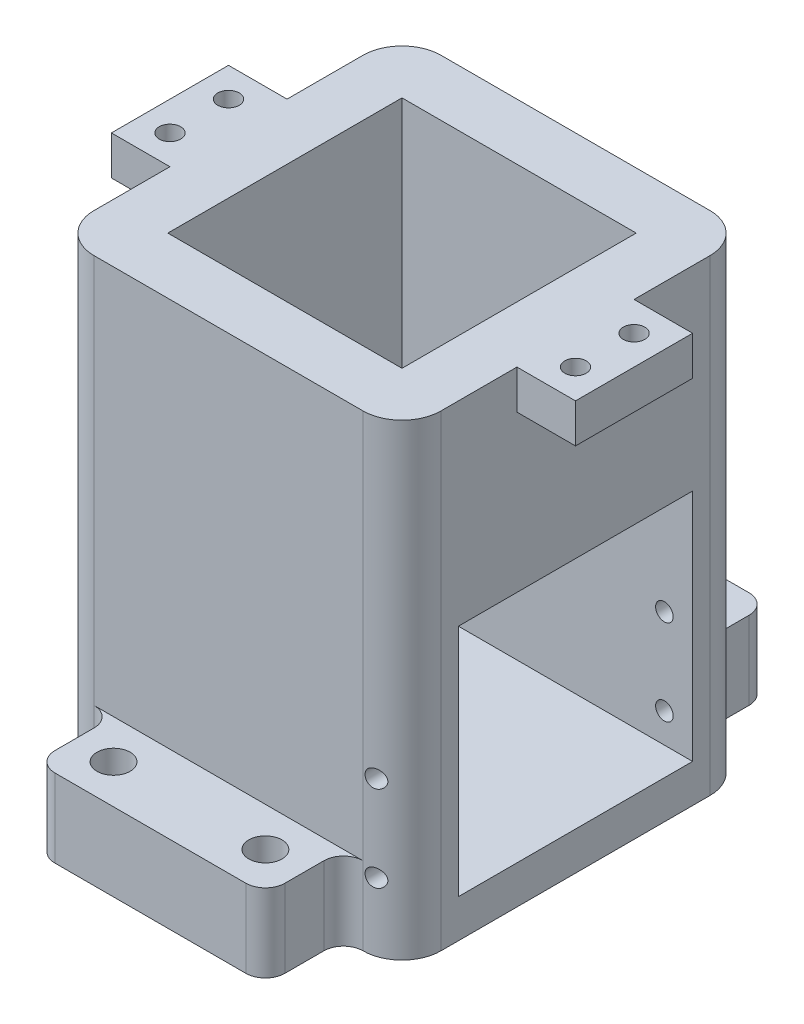
SolidWorks part; units mm, degrees
ref_plane "Front Plane" through (0, 0, 0) normal (0, 0, 1) x (1, 0, 0)
ref_plane "Top Plane" through (0, 0, 0) normal (0, 1, 0) x (1, 0, 0)
ref_plane "Right Plane" through (0, 0, 0) normal (1, 0, 0) x (0, 0, -1)
sketch "Sketch3" plane through (0, 0, 0) normal (0, 1, 0) x (1, 0, 0)
  line L1 (0, 0) -> (88.9, 0)
  line L2 (0, 0) -> (0, 88.9)
  line L3 (0, 88.9) -> (88.9, 88.9)
  line L4 (88.9, 0) -> (88.9, 88.9)
  dimension "D1" = 88.9
  dimension "D2" = 88.9
extrude "Boss-Extrude2" add sketch "Sketch3" along normal blind 50.8
ref_plane "Plane1" through (44.45, 0, 0) normal (-1, 0, 0) x (0, 0, 1)
sketch "Sketch5" plane through (0, 50.8, 0) normal (0, 1, 0) x (1, 0, 0)
  line L6 (0, 0) -> (88.9, 0)
  line L7 (0, 0) -> (0, 88.9)
  line L8 (0, 88.9) -> (88.9, 88.9)
  line L9 (88.9, 0) -> (88.9, 88.9)
sketch "Sketch7" plane through (0, 0, 0) normal (0, -1, 0) x (1, 0, 0)
  line L0 (44.45, -44.45) -> (65.45, -44.45)
  line L1 (44.45, 27.94) -> (44.45, -27.94) construction
  line L2 (65.45, -44.45) -> (65.45, -24.45)
  line L3 (65.45, -24.45) -> (23.45, -24.45)
  line L4 (23.45, -24.45) -> (23.45, -66.45)
  line L5 (23.45, -66.45) -> (65.45, -66.45)
  line L6 (65.45, -66.45) -> (65.45, -44.45)
  line L7 (44.45, -44.45) -> (44.45, -23.45)
  line L8 (44.45, -44.45) -> (44.45, -65.45)
  dimension "D1" = 21
  dimension "D3" = 42
  dimension "D4" = 42
  dimension "D5" = 21
  dimension "D6" = 21
sketch "Sketch10" plane through (0, 0, 0) normal (-1, 0, 0) x (0, 0, 1)
  line L1 (-73.9, 41) -> (-53.9, 41)
  line L2 (-73.9, 41) -> (-73.9, 61)
  line L3 (-73.9, 61) -> (-53.9, 61)
  line L4 (-53.9, 41) -> (-53.9, 61)
  line L5 (-88.9, 50.8) -> (-88.9, 0) construction
  line L6 (-35, 43.1973) -> (-15, 43.1973)
  line L7 (-35, 43.1973) -> (-35, 63.1973)
  line L8 (-35, 63.1973) -> (-15, 63.1973)
  line L9 (-15, 43.1973) -> (-15, 63.1973)
  line L11 (-88.9, 0) -> (0, 0) construction
  dimension "D1" = 20
  dimension "D2" = 20
  dimension "D3" = 20
  dimension "D4" = 20
  dimension "D5" = 18.9
  dimension "D6" = 15
  dimension "D7" = 41
sketch "Sketch11" plane through (88.9, 0, 0) normal (1, 0, 0) x (0, 0, -1)
  line L0 (0, 0) -> (88.9, 0) construction
  line L1 (15, 0) -> (35, 0)
  line L2 (15, 0) -> (15, 20)
  line L3 (15, 20) -> (35, 20)
  line L4 (35, 0) -> (35, 20)
  line L5 (0, 50.8) -> (0, 0) construction
  line L6 (53.9, 41) -> (73.9, 41)
  line L7 (53.9, 41) -> (53.9, 61)
  line L8 (53.9, 61) -> (73.9, 61)
  line L9 (73.9, 41) -> (73.9, 61)
  line L10 (88.9, 50.8) -> (88.9, 0) construction
  dimension "D1" = 20
  dimension "D2" = 20
  dimension "D3" = 15
  dimension "D4" = 15
sketch "Sketch13" plane through (0, 0, 0) normal (0, 0, 1) x (1, 0, 0)
  line L0 (44.45, 27.94) -> (44.45, -27.94) construction
  line L1 (0, 0) -> (88.9, 0) construction
  line L2 (88.9, 50.8) -> (88.9, 0) construction
  circle A0 centre (44.45, 20) radius 4.25
  dimension "D1" = 20
  dimension "D2" = 44.45
extrude "Cut-Extrude4" cut sketch "Sketch13" against normal blind 102
sketch "Sketch30" plane through (0, 50.8, 0) normal (0, 1, 0) x (1, 0, 0)
  line L1 (0, 0) -> (88.9, 0)
  line L2 (0, 0) -> (0, 88.9)
  line L3 (0, 88.9) -> (88.9, 88.9)
  line L4 (88.9, 0) -> (88.9, 88.9)
  line L5 (14.45, 74.45) -> (74.45, 74.45)
  line L6 (14.45, 74.45) -> (14.45, 14.45)
  line L7 (14.45, 14.45) -> (74.45, 14.45)
  line L8 (74.45, 74.45) -> (74.45, 14.45)
  dimension "D1" = 60
  dimension "D2" = 60
  dimension "D3" = 14.45
  dimension "D4" = 14.45
extrude "Boss-Extrude8" add sketch "Sketch30" along normal blind 110
sketch "Sketch31" plane through (0, 160.8, 0) normal (0, 1, 0) x (1, 0, 0)
  line L0 (0, 0) -> (0, 88.9) construction
  line L9 (0, 44.45) -> (-15, 44.45)
  line L10 (0, 44.45) -> (0, 59.45)
  line L11 (0, 59.45) -> (-15, 59.45)
  line L12 (-15, 44.45) -> (-15, 59.45)
  line L13 (88.9, 0) -> (88.9, 88.9) construction
  line L14 (0, 44.45) -> (-15, 44.45)
  line L15 (0, 44.45) -> (0, 29.45)
  line L16 (0, 29.45) -> (-15, 29.45)
  line L17 (-15, 44.45) -> (-15, 29.45)
  line L18 (88.9, 44.45) -> (103.9, 44.45)
  line L19 (88.9, 44.45) -> (88.9, 59.45)
  line L20 (88.9, 59.45) -> (103.9, 59.45)
  line L21 (103.9, 44.45) -> (103.9, 59.45)
  line L22 (0, 59.45) -> (0, 29.45)
  line L23 (88.9, 44.45) -> (103.9, 44.45)
  line L24 (88.9, 44.45) -> (88.9, 29.45)
  line L25 (88.9, 29.45) -> (103.9, 29.45)
  line L26 (103.9, 44.45) -> (103.9, 29.45)
  circle A6 centre (-7.5, 51.95) radius 2.75
  circle A7 centre (-7.5, 36.95) radius 2.75
  circle A8 centre (96.4, 51.95) radius 2.75
  circle A9 centre (96.4, 36.95) radius 2.75
  line M1 (0, 88.9) -> (0, 0)
  line M3 (88.9, 0) -> (88.9, 88.9)
  dimension "D1" = 15
  dimension "D5" = 15
  dimension "D2" = 15
  dimension "D3" = 15
  dimension "D4" = 15
  dimension "D6" = 15
  dimension "D7" = 15
  dimension "D8" = 15
extrude "Boss-Extrude10" add sketch "Sketch31" against normal blind 10 contours L12 L9 L11 A6 M1 | L9 L17 L16 A7 M1 | L18 L21 L20 A8 M3 | L26 L18 L25 A9 M3 region at (-0.2121, 160.8, -36.95) region at (-7.5, 160.8, -44.6621) region at (89.1121, 160.8, -51.95) region at (96.4, 160.8, -44.2379)
fillet "Fillet1" radius 10 4 edges at (0, 80.4, 0) (0, 80.4, -88.9) (88.9, 80.4, -88.9) (88.9, 80.4, 0)
sketch "Sketch33" plane through (88.9, 0, 0) normal (1, 0, 0) x (0, 0, -1)
  line L1 (14.45, 50.8) -> (74.45, 50.8)
  line L2 (14.45, 50.8) -> (14.45, 110.8)
  line L3 (14.45, 110.8) -> (74.45, 110.8)
  line L4 (74.45, 50.8) -> (74.45, 110.8)
  line L8 (0, 160.8) -> (0, 0) construction
  dimension "D1" = 60
  dimension "D2" = 60
  dimension "D3" = 14.45
extrude "Cut-Extrude5" cut sketch "Sketch33" against normal blind 20
sketch "Sketch36" plane through (88.9, 0, 0) normal (1, 0, 0) x (0, 0, -1)
  line L0 (0, 160.8) -> (0, 0) construction
  point P0 (0, 80.4)
sketch "Sketch37" plane through (0, 0, 0) normal (0, 0, 1) x (1, 0, 0)
  line L0 (88.9, 160.8) -> (88.9, 0) construction
  circle A0 centre (81.675, 80.4) radius 2.25
  circle A1 centre (81.675, 58.4) radius 2.25
  dimension "D1" = 7.225
  dimension "D2" = 7.225
  dimension "D3" = 22
extrude "Cut-Extrude6" cut sketch "Sketch37" against normal blind 113
sketch "Sketch38" plane through (0, 0, 0) normal (0, -1, 0) x (1, 0, 0)
  line L1 (88.9, -88.9) -> (0, -88.9)
  line L2 (88.9, -88.9) -> (88.9, 0)
  line L3 (88.9, 0) -> (0, 0)
  line L4 (0, -88.9) -> (0, 0)
  line L5 (88.9, -88.9) -> (0, 0) construction
  line L6 (88.9, 0) -> (0, -88.9) construction
  point P0 (44.45, -44.45)
extrude "Cut-Extrude7" cut sketch "Sketch38" against normal blind 41
sketch "Sketch39" plane through (0, 0, 0) normal (0, 0, 1) x (1, 0, 0)
  line L0 (78.9, 41) -> (10, 41) construction
  line L1 (44.45, 41) -> (73.9, 41)
  line L2 (44.45, 41) -> (44.45, 61)
  line L3 (44.45, 61) -> (73.9, 61)
  line L4 (73.9, 41) -> (73.9, 61)
  line L6 (44.45, 41) -> (15, 41)
  line L7 (44.45, 41) -> (44.45, 61)
  line L8 (44.45, 61) -> (15, 61)
  line L9 (15, 41) -> (15, 61)
  line M7 (10, 41) -> (78.9, 41)
  dimension "D1" = 29.45
  dimension "D2" = 29.45
  dimension "D3" = 20
sketch "Sketch40" plane through (0, 0, -88.9) normal (0, 0, -1) x (-1, 0, 0)
  line L1 (-44.45, 41) -> (-15, 41)
  line L2 (-44.45, 41) -> (-44.45, 61)
  line L3 (-44.45, 61) -> (-15, 61)
  line L4 (-15, 41) -> (-15, 61)
  line L5 (-44.45, 41) -> (-73.9, 41)
  line L6 (-44.45, 41) -> (-44.45, 61)
  line L7 (-44.45, 61) -> (-73.9, 61)
  line L8 (-73.9, 41) -> (-73.9, 61)
  line M7 (-78.9, 41) -> (-10, 41)
  dimension "D1" = 29.45
  dimension "D2" = 29.45
  dimension "D3" = 20
extrude "Boss-Extrude11" add sketch "Sketch39" along normal blind 20 contours L9 L2 L8 M7 | L4 L3 L2 M7 region at (59.175, 51, 0) region at (29.725, 51, 0)
extrude "Boss-Extrude12" add sketch "Sketch40" along normal blind 20 contours L8 L2 L7 M7 | L4 L3 L2 M7 region at (29.725, 51, -88.9) region at (59.175, 51, -88.9)
sketch "Sketch41" plane through (0, 41, 0) normal (0, -1, 0) x (1, 0, 0)
  line L0 (73.9, 20) -> (73.9, 0) construction
  line L1 (15, 20) -> (73.9, 20) construction
  line L2 (15, 20) -> (15, 0) construction
  line L3 (73.9, -108.9) -> (15, -108.9) construction
  line L4 (73.9, -108.9) -> (73.9, -88.9) construction
  line L5 (15, -108.9) -> (15, -88.9) construction
  circle A0 centre (63.9, 10) radius 4.25
  circle A1 centre (25, 10) radius 4.25
  circle A2 centre (63.9, -98.9) radius 4.25
  circle A3 centre (25, -98.9) radius 4.25
  dimension "D1" = 10
  dimension "D2" = 10
  dimension "D3" = 10
  dimension "D4" = 10
  dimension "D5" = 10
  dimension "D6" = 10
  dimension "D7" = 10
  dimension "D8" = 10
extrude "Cut-Extrude8" cut sketch "Sketch41" against normal blind 20
fillet "Fillet2" radius 5 8 edges at (15, 51, -108.9) (15, 51, -88.9) (73.9, 51, -108.9) (73.9, 51, -88.9) (73.9, 51, 0) (15, 51, 0) (15, 51, 20) (73.9, 51, 20)
